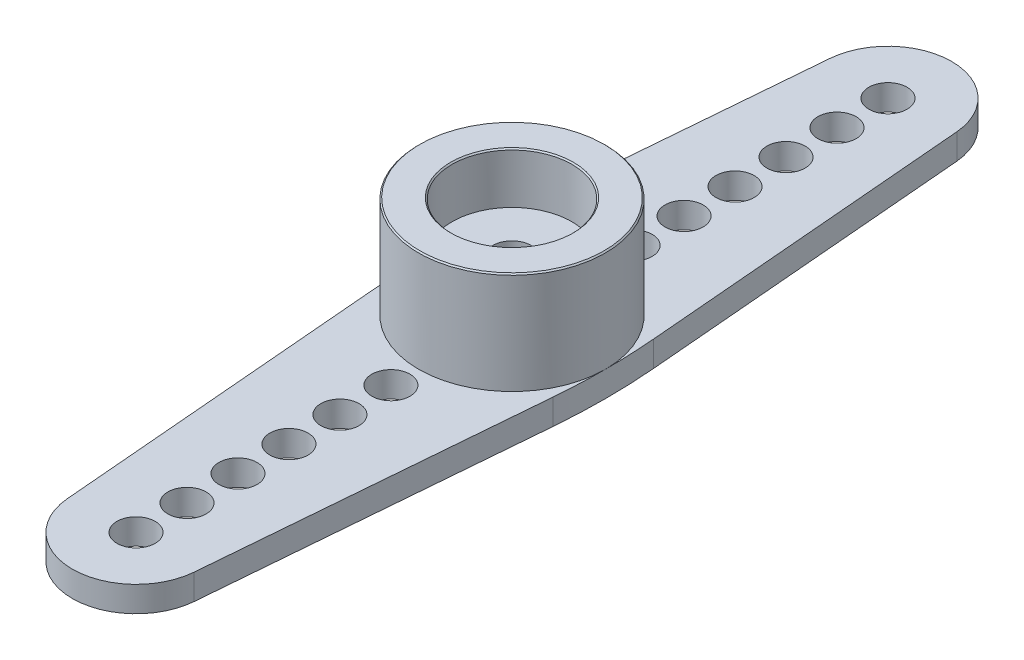
SolidWorks part; units mm, degrees
ref_plane "Front Plane" through (0, 0, 0) normal (0, 0, 1) x (1, 0, 0)
ref_plane "Top Plane" through (0, 0, 0) normal (0, 1, 0) x (1, 0, 0)
ref_plane "Right Plane" through (0, 0, 0) normal (1, 0, 0) x (0, 0, -1)
sketch "Sketch1" plane through (0, 0, 0) normal (0, 1, 0) x (1, 0, 0)
  line L0 (0, -14.75) -> (0, 14.75) construction
  line L1 (-2.5, -14.75) -> (-2.5, 14.75) construction
  line L2 (2.5, -14.75) -> (2.5, 14.75) construction
  line L3 (-2.4912, 14.9596) -> (-3.5842, 1.9707)
  line L4 (-3.5842, -1.9707) -> (-2.4912, -14.9596)
  line L5 (0, 0) -> (0, -22.2241) construction
  line L6 (3.5842, -1.9707) -> (2.4912, -14.9596)
  line L7 (2.4912, 14.9596) -> (3.5842, 1.9707)
  line L8 (0, 0) -> (13.9069, 0) construction
  arc A0 (-2.5, -14.75) -> (2.5, -14.75) centre (0, -14.75) ccw construction
  arc A1 (2.5, 14.75) -> (-2.5, 14.75) centre (0, 14.75) ccw construction
  arc A2 (-2.4912, 14.9596) -> (2.4912, 14.9596) centre (0, 14.75) cw
  arc A3 (-2.4912, -14.9596) -> (2.4912, -14.9596) centre (0, -14.75) ccw
  circle A4 centre (0, 14.75) radius 0.75
  arc A5 (3.5842, -1.9707) -> (3.5842, 1.9707) centre (-19.8361, 0) ccw
  arc A6 (-3.5842, 1.9707) -> (-3.5842, -1.9707) centre (19.8361, 0) ccw
  circle A7 centre (0, 0) radius 3.6669 construction
  circle A8 centre (0, 12.75) radius 0.75
  circle A9 centre (0, 10.75) radius 0.75
  circle A10 centre (0, 8.75) radius 0.75
  circle A11 centre (0, 6.75) radius 0.75
  circle A12 centre (0, 4.75) radius 0.75
  circle A13 centre (0, 0) radius 0.75
  circle A14 centre (0, -14.75) radius 0.75
  circle A15 centre (0, -12.75) radius 0.75
  circle A16 centre (0, -10.75) radius 0.75
  circle A17 centre (0, -8.75) radius 0.75
  circle A18 centre (0, -6.75) radius 0.75
  circle A19 centre (0, -4.75) radius 0.75
  point P2 (0, 0)
  point P21 (3.75, 0)
  point P24 (-3.75, 0)
  dimension "D2" = 2.5
  dimension "D4" = 1.5
  dimension "D5" = 23.503
  dimension "D1" = 29.5
  dimension "D3" = 3.75
  dimension "D7" = 2
  dimension "D6" = 6
extrude "Boss-Extrude1" add sketch "Sketch1" along normal blind 1
sketch "Sketch2" plane through (0, 0, 0) normal (0, -1, 0) x (1, 0, 0)
  circle A0 centre (0, 0) radius 3.6669 construction
  circle A1 centre (0, 0) radius 3.6669
  circle A2 centre (0, 0) radius 1.5
  circle M18 centre (0, 0) radius 0.75
  dimension "D1" = 3
extrude "Boss-Extrude2" add sketch "Sketch2" against normal blind 5 contours A2 M18 | A1 A2 region at (-3.5632, 0, 0) region at (-1.4576, 0, 0)
extrude "Cut-Extrude1" cut sketch "Sketch2<2>" against normal blind 0.5 contours A2
sketch "Sketch2<2>" plane through (0, 0, 0) normal (0, -1, 0) x (1, 0, 0) same geometry as "Sketch2"
sketch "Sketch3" plane through (0, 5, 0) normal (0, 1, 0) x (1, 0, 0)
  circle A0 centre (0, 0) radius 2.355
  dimension "D1" = 4.71
extrude "Cut-Extrude2" cut sketch "Sketch3" against normal blind 2
chamfer "Chamfer1" distance 0.05 angle 45 2 edges at (0, 5, -3.6669) (0, 5, 2.355)
